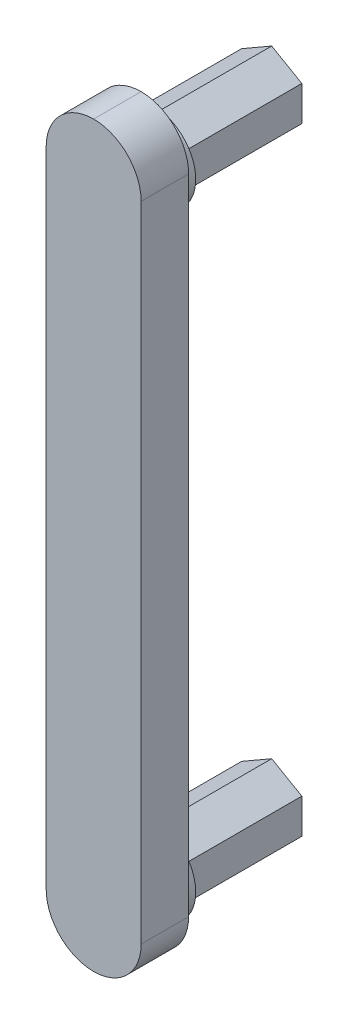
SolidWorks part; units mm, degrees
material "PETG"
ref_plane "Front Plane" through (0, 0, 0) normal (0, 0, 1) x (1, 0, 0)
ref_plane "Top Plane" through (0, 0, 0) normal (0, 1, 0) x (1, 0, 0)
ref_plane "Right Plane" through (0, 0, 0) normal (1, 0, 0) x (0, 0, -1)
sketch "Sketch1" plane through (0, 0, 0) normal (0, 0, 1) x (1, 0, 0)
  line L1 (-10, 77.75) -> (10, 77.75)
  line L2 (-10, 77.75) -> (-10, -77.75)
  line L3 (-10, -77.75) -> (10, -77.75)
  line L4 (10, 77.75) -> (10, -77.75)
  point P8 (-10, 0)
  point P9 (0, 77.75)
  dimension "D1" = 20
  dimension "D2" = 155.5
extrude "Boss-Extrude1" add sketch "Sketch1" along normal blind 10
sketch "Sketch2" plane through (0, 0, 0) normal (0, 0, -1) x (-1, 0, 0)
  line L0 (0, 65) -> (0, -65) construction
  circle A0 centre (0, 65) radius 9
  circle A1 centre (0, -65) radius 9
  dimension "D1" = 130
  dimension "D2" = 18
extrude "Boss-Extrude2" add sketch "Sketch2" along normal blind 2.5
fillet "Fillet1" radius 10 4 edges at (10, -77.75, 5) (-10, -77.75, 5) (-10, 77.75, 5) (10, 77.75, 5)
sketch "Sketch3" plane through (0, 0, -2.5) normal (0, 0, -1) x (-1, 0, 0)
  line L0 (0, 0) -> (50000, 0) construction
  line L1 (0, 57.6734) -> (6.345, 61.3367)
  line L2 (6.345, 61.3367) -> (6.345, 68.6633)
  line L3 (6.345, 68.6633) -> (0, 72.3266)
  line L4 (0, 72.3266) -> (-6.345, 68.6633)
  line L5 (-6.345, 68.6633) -> (-6.345, 61.3367)
  line L6 (-6.345, 61.3367) -> (0, 57.6734)
  line L7 (-6.345, -61.3367) -> (0, -57.6734)
  line L8 (-6.345, -68.6633) -> (-6.345, -61.3367)
  line L9 (0, -72.3266) -> (-6.345, -68.6633)
  line L10 (6.345, -68.6633) -> (0, -72.3266)
  line L11 (6.345, -61.3367) -> (6.345, -68.6633)
  line L12 (0, -57.6734) -> (6.345, -61.3367)
  circle A0 centre (0, 65) radius 6.345 construction
  circle A1 centre (0, -65) radius 6.345 construction
  dimension "D1" = 12.69
extrude "Boss-Extrude3" add sketch "Sketch3" along normal blind 25
sketch "Sketch4" plane through (0, 0, -27.5) normal (0, 0, -1) x (-1, 0, 0)
  circle A0 centre (0, 65) radius 1.985
  circle A1 centre (0, 65) radius 9 construction
  circle A2 centre (0, -65) radius 1.985
  circle A3 centre (0, -65) radius 9 construction
  dimension "D1" = 3.97
extrude "Cut-Extrude1" cut sketch "Sketch4" against normal blind 12
equation "\"tol_dia_id_intfc\" = 0.0200mm ' For hole diameters - Interference fit"
equation "\"tol_dia_id_slip\"  = 0.0300mm ' For hole diameters - Slip fit"
equation "\"tol_dia_id_clear\" = 0.0500mm ' For hole diameters - Clearance fit"
equation "\"tol_dia_od_intfc\" = 0.0200mm ' For shaft diameters - Interference fit"
equation "\"tol_dia_od_slip\"  = 0.0300mm ' For shaft diameters - Slip fit"
equation "\"tol_dia_od_clear\" = 0.0500mm ' For shaft diameters - Clearance fit"
equation "\"tol_general_intfc\"= 0.0030mm ' For general parts (Horiz) - Interference fit"
equation "\"tol_general_slip\" = 0.0050mm ' For general parts (Horiz) - Slip fit"
equation "\"tol_general_clear\"= 0.0100mm ' For general parts (Horiz) - Clearance fit"
equation "\"tol_layer_intfc\"  = 0.0030mm ' For all parts (Vert) - Interference fit"
equation "\"tol_layer_slip\"   = 0.0050mm ' For all parts (Vert) - Slip fit"
equation "\"tol_layer_clear\"  = 0.0100mm ' For all parts (Vert) - Clearance fit"
equation "\"tol_corner_rad\"   = 0.100mm ' For corners that fit into other parts"
equation "\"D1@Sketch3\"=12.7 - \"tol_general_slip\"*2"
equation "\"D1@Sketch4\"=3.95+\"tol_dia_id_intfc\""
